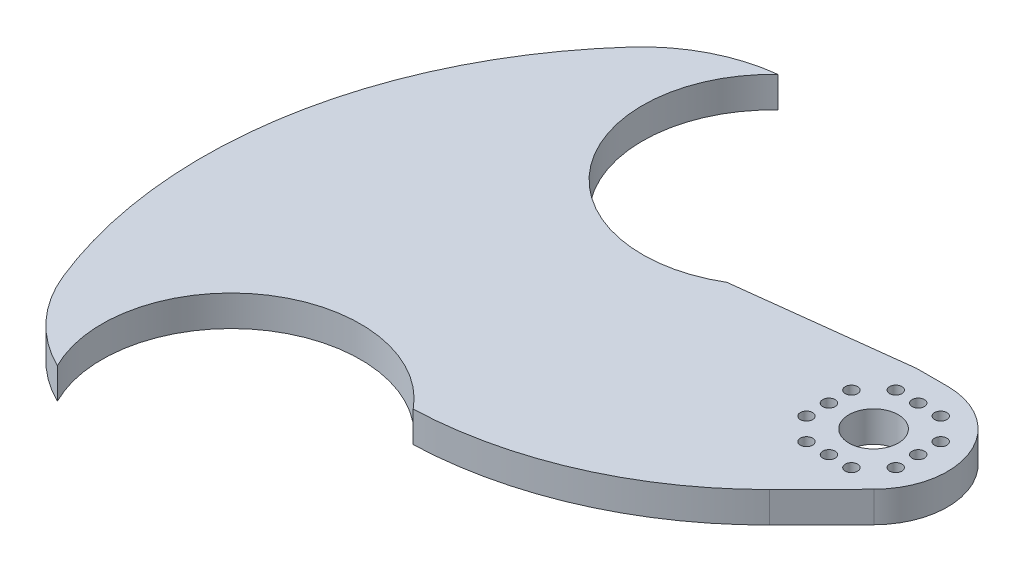
SolidWorks part; units mm, degrees
ref_plane "Plan de face" through (0, 0, 0) normal (0, 0, 1) x (1, 0, 0)
ref_plane "Plan de dessus" through (0, 0, 0) normal (0, 1, 0) x (1, 0, 0)
ref_plane "Plan de droite" through (0, 0, 0) normal (1, 0, 0) x (0, 0, -1)
sketch "Esquisse1" plane through (0, 0, 0) normal (0, 1, 0) x (1, 0, 0)
  line L0 (7.25, 3.65) -> (7.25, -3.65) construction
  line L1 (0, 0) -> (7.25, 0) construction
  line L2 (-32.5252, 8.6926) -> (-5, 12)
  line L3 (0, 12) -> (-5, 12)
  line L5 (0.0794, -16.9704) -> (8.5249, -8.4455)
  line L12 (0, 0) -> (-90, 0) construction
  line L13 (-64.0612, -34.9874) -> (-54.853, 17.2348) construction
  line L14 (-65, 0) -> (-64.0612, -34.9874) construction
  arc A0 (-40.1584, -34.5969) -> (0.0794, -16.9704) centre (-42.2857, 25) ccw
  arc A3 (-18.7097, 12.7453) -> (-21.4912, -44.9899) centre (-17.71, -16.2374) ccw construction
  circle A4 centre (0, 0) radius 4
  circle A5 centre (7.25, -3.65) radius 1
  circle A6 centre (7.25, 0) radius 1
  circle A7 centre (7.25, 3.65) radius 1
  circle A8 centre (3.65, -7.25) radius 1
  circle A9 centre (0, -7.25) radius 1
  circle A10 centre (-3.65, -7.25) radius 1
  circle A11 centre (-7.25, -3.65) radius 1
  circle A12 centre (-7.25, 0) radius 1
  circle A13 centre (-7.25, 3.65) radius 1
  circle A14 centre (-3.65, 7.25) radius 1
  circle A15 centre (0, 7.25) radius 1
  circle A16 centre (3.65, 7.25) radius 1
  arc A36 (-54.853, 17.2348) -> (-64.0612, -34.9874) centre (-17.71, -16.2374) ccw construction
  arc A37 (-73.4246, 33.971) -> (-87.2369, -44.3624) centre (-17.71, -16.2374) ccw
  arc A40 (-87.2369, -44.3624) -> (-75.1385, -57.3993) centre (-64.0612, -34.9874) ccw
  arc A41 (8.5249, -8.4455) -> (0, 12) centre (0, 0) ccw
  arc A42 (-17.7875, 33.7625) -> (-48.8394, -55.365) centre (-17.71, -16.2374) ccw construction
  arc A43 (-57.597, 42.0838) -> (-32.5252, 8.6926) centre (-43.2535, 26.7454) ccw
  arc A44 (-57.597, 42.0838) -> (-73.4246, 33.971) centre (-54.853, 17.2348) ccw
  arc A45 (-40.1584, -34.5969) -> (-75.1385, -57.3993) centre (-56.4141, -47.8917) ccw
  point P39 (0, 0)
  point P78 (-56.6847, 2.6915)
  point P85 (-65, 0)
  dimension "D4" = 25
  dimension "D5" = 12
  dimension "D6" = 21
  dimension "D7" = 25
  dimension "D8" = 25
  dimension "D9" = 7.25
  dimension "D10" = 5
  dimension "D18" = 90
  dimension "D20" = 75
  dimension "D26" = 12
  dimension "D13" = 50
  dimension "D14" = 21
  dimension "D15" = 7.3
  dimension "D22" = 35
  dimension "D23" = 80
  dimension "D24" = 20
  dimension "D25" = 25
  dimension "D30" = 15
  dimension "D32" = 15
extrude "Boss.-Extru.1" add sketch "Esquisse1" along normal blind 5
